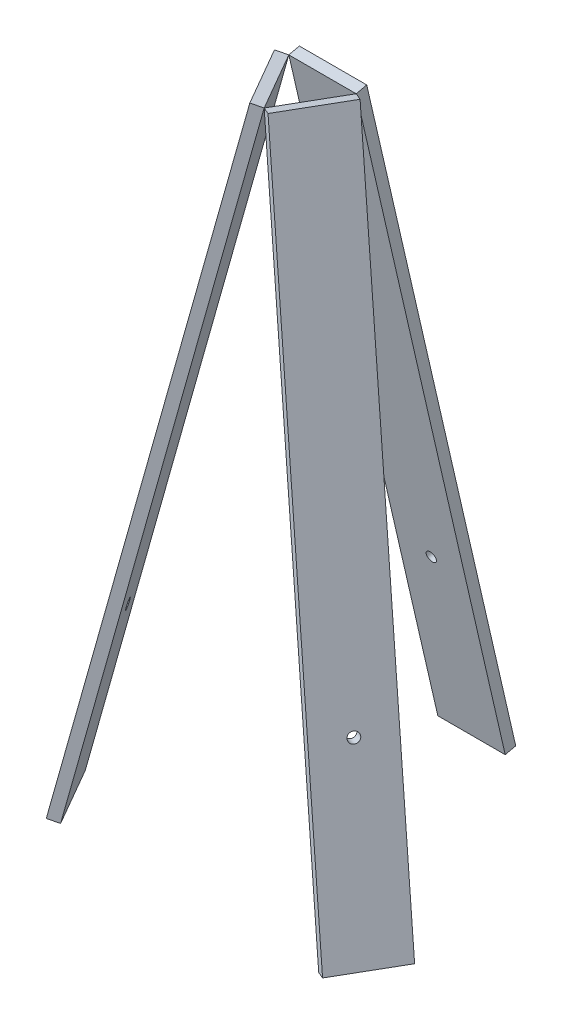
SolidWorks part; units mm, degrees
ref_plane "前视基准面" through (0, 0, 0) normal (0, 0, 1) x (1, 0, 0)
ref_plane "上视基准面" through (0, 0, 0) normal (0, 1, 0) x (1, 0, 0)
ref_plane "右视基准面" through (0, 0, 0) normal (1, 0, 0) x (0, 0, -1)
other "Configuration Table"
sketch "草图1" plane through (0, 10, 0) normal (0, 1, 0) x (1, 0, 0)
  line L0 (0, 0) -> (0, 25) construction
  line L1 (-5, 25) -> (5, 25)
  dimension "D1" = 10
  dimension "D2" = 25
sketch "草图2" plane through (0, 0, 0) normal (1, 0, 0) x (0, 0, -1)
  line L0 (25, 10) -> (2.8868, 106)
  line L1 (0, 10) -> (25, 10) construction
  line L2 (2.8868, 106) -> (0, 106)
  line L3 (0, 106) -> (0, 0) construction
  dimension "D1" = 2.8868
  dimension "D2" = 96
ref_plane "基准面1" through (0, 106, 0) normal (0, -1, 0) x (-1, 0, 0)
sketch "草图3" plane through (0, 106, 0) normal (0, -1, 0) x (-1, 0, 0)
  line L0 (-5, 2.8868) -> (5, 2.8868)
  line L1 (0, 0) -> (0, 25) construction
  line L2 (0, 0) -> (0, 2.8868) construction
  dimension "D1" = 5
ref_plane "基准面2" through (0, 5.9724, -25.9278) normal (0, -0.2245, 0.9745) x (1, 0, 0)
sketch "草图4" plane through (0, 5.9724, -25.9278) normal (0, -0.2245, 0.9745) x (1, 0, 0)
  line L0 (5, 102.647) -> (-5, 102.647) construction
  line L1 (-5, 4.1331) -> (5, 4.1331) construction
  line L2 (5, 102.647) -> (-5, 102.647)
  line L3 (-5, 4.1331) -> (5, 4.1331)
  line L4 (-5, 102.647) -> (-5, 4.1331)
  line L5 (5, 4.1331) -> (5, 102.647)
extrude "凸台-拉伸1" add sketch "草图4" against normal blind 1.6
sketch "草图5" plane through (0, 5.9724, -25.9278) normal (0, -0.2245, 0.9745) x (1, 0, 0)
  circle A0 centre (0, 30.722) radius 0.75 construction
  circle A1 centre (0, 30.722) radius 0.75
extrude "切除-拉伸1" cut sketch "草图5" against normal through all
ref_axis "基准轴1" through (0, 108.058, 0) along (0, -1, 0)
pattern_circular "阵列(圆周)3" count 3 over 360 about axis through (0, 108.058, 0) along (0, -1, 0) of bodies 111 106
